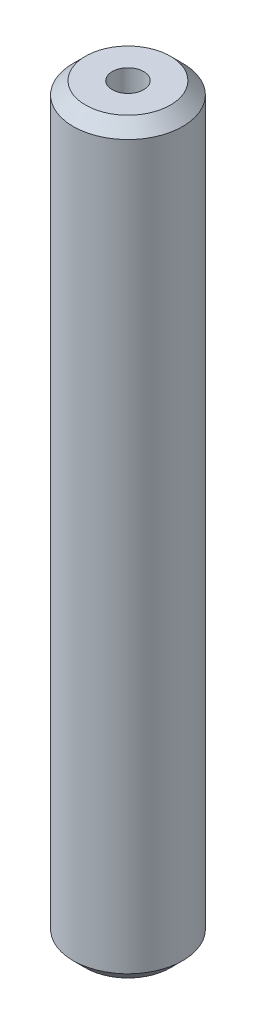
SolidWorks part; units mm, degrees
ref_plane "Front Plane" through (0, 0, 0) normal (0, 0, 1) x (1, 0, 0)
ref_plane "Top Plane" through (0, 0, 0) normal (0, 1, 0) x (1, 0, 0)
ref_plane "Right Plane" through (0, 0, 0) normal (1, 0, 0) x (0, 0, -1)
sketch "Sketch1" plane through (0, 0, 0) normal (0, 1, 0) x (1, 0, 0)
  circle A0 centre (0, 0) radius 5
  dimension "SHAFT_OD" = 10
extrude "Boss-Extrude1" add sketch "Sketch1" along normal blind 68.2226
sketch "Sketch2" plane through (0, 0, 0) normal (0, 1, 0) x (1, 0, 0)
  circle A0 centre (0, 0) radius 1.4371
  dimension "BORE_D" = 2.8742
extrude "Cut-Extrude1" cut sketch "Sketch2" along normal through all
chamfer "Chamfer1" distance 1.1285 angle 45 2 edges at (0, 68.2226, 5) (0, 0, 5)
